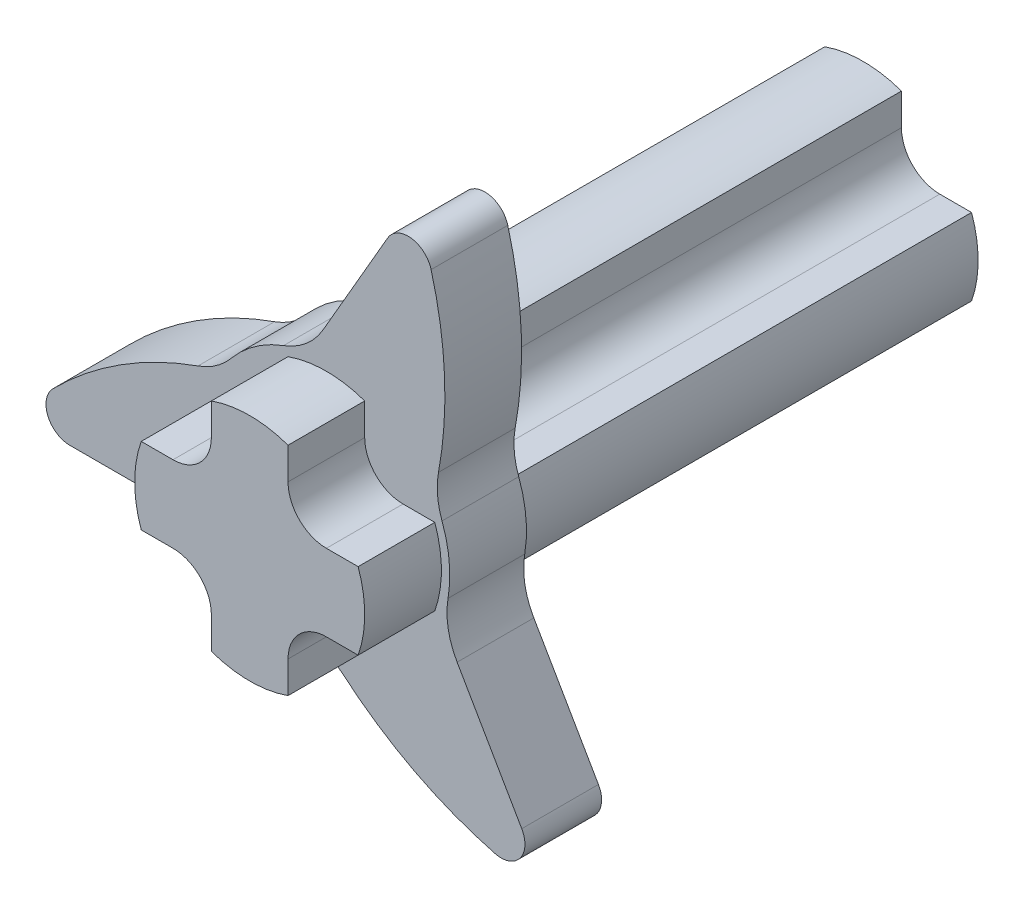
SolidWorks part; units mm, degrees
note: '?' marks a value the reader was unsure of. The reader was unsure of these and kept them because the rebuilt part matched: shared geometry of "Sketch1<3>".
ref_plane "Front Plane" through (0, 0, 0) normal (1, 0, 0) x (0, 1, 0)
ref_plane "Top Plane" through (0, 0, 0) normal (0, 0, 1) x (0, 1, 0)
ref_plane "Right Plane" through (0, 0, 0) normal (0, 1, 0) x (-1, 0, 0)
ref_plane "cam start" through (0, 0, 600) normal (0, 0, 1) x (0, 1, 0)
sketch "Sketch1" plane through (0, 0, 0) normal (0, 0, 1) x (0, 1, 0)
  line L1 (-50, 141.4214) -> (-50, 0)
  line L2 (50, 141.4214) -> (50, 0)
  line L3 (-50, 0) -> (50, 0)
  arc A0 (50, 141.4214) -> (-50, 141.4214) centre (0, 0) ccw
  point P3 (0, 0)
  dimension "D1" = 150
  dimension "D2" = 100
extrude "Boss-Extrude1" add sketch "Sketch1" along normal up to surface (600 mm away) up to plane "cam start"
ref_axis "Axis1" through (0, 0, -10) along (0, 0, 1)?
pattern_circular "CirPattern1" count 4 over 360 about axis through (0, 0, 0) along (0, 0, 1) of bodies 101
combine bodies "Combine1" bodies to combine 101 102 103 104
fillet "Fillet1" radius 50 4 edges at (-50, 50, 300) (-50, -50, 300) (50, -50, 300) (50, 50, 300)
ref_plane "cam end" through (0, 0, 700) normal (0, 0, 1) x (0, 1, 0)
sketch "Sketch4" plane through (0, 0, 600) normal (0, 0, 1) x (0, 1, 0)
  circle A0 centre (0, 0) radius 160
  arc A2 (50, 141.4214) -> (-50, 141.4214) centre (0, 0) ccw construction
  dimension "D1" = 10
extrude "Boss-Extrude3" add sketch "Sketch4" along normal up to surface (100 mm away) up to plane "cam end"
sketch "Sketch3" plane through (0, 0, 600) normal (0, 0, 1) x (0, 1, 0)
  line L0 (-100, 0) -> (-100, 400)
  line L1 (-100, 0) -> (100, 0)
  arc A1 (100, 0) -> (-100, 400) centre (-400, 0) ccw
  point P6 (0, 0)
  dimension "D1" = 400
  dimension "D2" = 200
extrude "Boss-Extrude2" add sketch "Sketch3" along normal up to surface (100 mm away) separate body up to plane "cam end"
fillet "Fillet2" radius 30 1 edges at (-400, -100, 650)
pattern_circular "CirPattern2" count 3 over 360 about axis through (0, 0, 0) along (0, 0, 1) of bodies 106
combine bodies "Combine2" bodies to combine 110 106 108 107
fillet "Fillet4" radius 100 6 edges at (-0.578, -159.999, 650) (-124.9, -100, 650) (149.0525, -58.1665, 650) (138.8521, 79.499, 650) (-24.1526, 158.1665, 650) (-138.2742, 80.5, 650)
sketch "Sketch5" plane through (0, 0, 700) normal (0, 0, 1) x (0, 1, 0)
  line L0 (-239.8275, -253.9345) -> (-93.8749, -169.6688) construction
  line L1 (339.8275, -80.7295) -> (193.8749, 3.5363) construction
  line L2 (-100, 334.664) -> (-100, 166.1325) construction
  line L3 (-239.8275, -253.9345) -> (-93.8749, -169.6688)
  line L4 (339.8275, -80.7295) -> (193.8749, 3.5363)
  line L5 (-100, 334.664) -> (-100, 166.1325)
  arc A0 (-123.0769, 102.2354) -> (-100, 166.1325) centre (-200, 166.1325) ccw construction
  arc A1 (-123.0769, 102.2354) -> (-157.7899, 26.5018) centre (0, 0) ccw construction
  arc A2 (-180.3405, -21.8472) -> (-157.7899, 26.5018) centre (-256.4086, 43.0654) ccw construction
  arc A3 (-180.3405, -21.8472) -> (-283.8591, -220.3927) centre (200, -346.4102) ccw construction
  arc A4 (-283.8591, -220.3927) -> (-239.8275, -253.9345) centre (-254.8275, -227.9538) ccw construction
  arc A5 (-27, -157.7054) -> (-93.8749, -169.6688) centre (-43.8749, -256.2713) ccw construction
  arc A6 (-27, -157.7054) -> (55.9438, -149.901) centre (0, 0) ccw construction
  arc A7 (109.0905, -145.2558) -> (55.9438, -149.901) centre (90.9086, -243.589) ccw construction
  arc A8 (109.0905, -145.2558) -> (332.7952, -135.6328) centre (200, 346.4102) ccw construction
  arc A9 (332.7952, -135.6328) -> (339.8275, -80.7295) centre (324.8275, -106.7102) ccw construction
  arc A10 (150.0769, 55.4701) -> (193.8749, 3.5363) centre (243.8749, 90.1388) ccw construction
  arc A11 (150.0769, 55.4701) -> (101.8462, 123.3992) centre (0, 0) ccw construction
  arc A12 (71.25, 167.1031) -> (101.8462, 123.3992) centre (165.5, 200.5237) ccw construction
  arc A13 (71.25, 167.1031) -> (-48.9362, 356.0255) centre (-400, 0) ccw construction
  arc A14 (-48.9362, 356.0255) -> (-100, 334.664) centre (-70, 334.664) ccw construction
  arc A15 (-123.0769, 102.2354) -> (-100, 166.1325) centre (-200, 166.1325) ccw
  arc A16 (-123.0769, 102.2354) -> (-157.7899, 26.5018) centre (0, 0) ccw
  arc A17 (-180.3405, -21.8472) -> (-157.7899, 26.5018) centre (-256.4086, 43.0654) ccw
  arc A18 (-180.3405, -21.8472) -> (-283.8591, -220.3927) centre (200, -346.4102) ccw
  arc A19 (-283.8591, -220.3927) -> (-239.8275, -253.9345) centre (-254.8275, -227.9538) ccw
  arc A20 (-27, -157.7054) -> (-93.8749, -169.6688) centre (-43.8749, -256.2713) ccw
  arc A21 (-27, -157.7054) -> (55.9438, -149.901) centre (0, 0) ccw
  arc A22 (109.0905, -145.2558) -> (55.9438, -149.901) centre (90.9086, -243.589) ccw
  arc A23 (109.0905, -145.2558) -> (332.7952, -135.6328) centre (200, 346.4102) ccw
  arc A24 (332.7952, -135.6328) -> (339.8275, -80.7295) centre (324.8275, -106.7102) ccw
  arc A25 (150.0769, 55.4701) -> (193.8749, 3.5363) centre (243.8749, 90.1388) ccw
  arc A26 (150.0769, 55.4701) -> (101.8462, 123.3992) centre (0, 0) ccw
  arc A27 (71.25, 167.1031) -> (101.8462, 123.3992) centre (165.5, 200.5237) ccw
  arc A28 (71.25, 167.1031) -> (-48.9362, 356.0255) centre (-400, 0) ccw
  arc A29 (-48.9362, 356.0255) -> (-100, 334.664) centre (-70, 334.664) ccw
extrude "Extrude-Thin1" add sketch "Sketch5" against normal up to surface (100 mm away) thin
ref_plane "extension" through (0, 0, 800) normal (0, 0, 1) x (0, 1, 0)
extrude "Boss-Extrude4" add sketch "Sketch1<3>" along normal up to surface (100 mm away) from surface at 700 separate body up to plane "extension" starting at plane "cam end"
sketch "Sketch1<3>" plane through (0, 0, 0) normal (0, 0, 1) x (0, 1, 0) same geometry as "Sketch1"
pattern_circular "CirPattern3" count 4 over 360 about axis through (0, 0, 0) along (0, 0, 1) of bodies 112
combine bodies "Combine3" bodies to combine 112 115 113 114
fillet "Fillet3" radius 50 4 edges at (50, 50, 750) (50, -50, 750) (-50, 50, 750) (-50, -50, 750)
